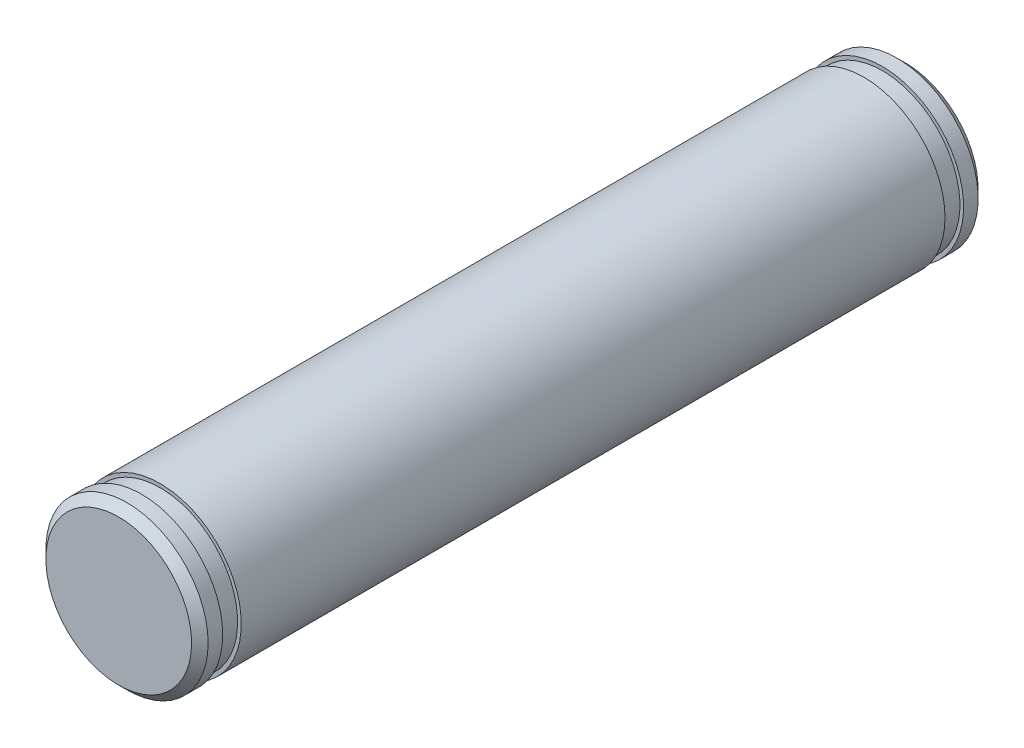
SolidWorks part; units mm, degrees
material "PET"
ref_plane "Front Plane" through (0, 0, 0) normal (0, 0, 1) x (1, 0, 0)
ref_plane "Top Plane" through (0, 0, 0) normal (0, 1, 0) x (1, 0, 0)
ref_plane "Right Plane" through (0, 0, 0) normal (1, 0, 0) x (0, 0, -1)
ref_axis "X AXIS" through (-88.99, 0, 0) along (1, 0, 0)
ref_axis "Y AXIS" through (0, 55, 0) along (0, -1, 0)
ref_axis "Z AXIS" through (0, 0, -88.99) along (0, 0, 1)
sketch "Sketch1" plane through (0, 0, 0) normal (1, 0, 0) x (0, 0, -1)
  line L0 (0, 0) -> (-23.504, 0) construction
  line L1 (0, 0) -> (60.325, 0)
  line L2 (0, 0) -> (0, 6.223)
  line L3 (0, 6.223) -> (60.325, 6.223)
  line L4 (60.325, 0) -> (60.325, 6.223)
  line L5 (88.99, 0) -> (-88.99, 0) construction
  dimension "D1" = 60.325
  dimension "D2" = 12.446
revolve "Revolve1" add sketch "Sketch1" angle 360 about L0
sketch "Sketch2" plane through (0, 0, 0) normal (1, 0, 0) x (0, 0, -1)
  line L5 (60.325, 6.223) -> (0, 6.223) construction
  line L6 (0, 0) -> (-9.7136, 0) construction
  line L7 (60.325, -6.223) -> (60.325, 6.223) construction
  line L8 (1.7526, 5.9436) -> (3.175, 5.9436)
  line L9 (1.7526, 5.9436) -> (1.7526, 6.7564)
  line L10 (1.7526, 6.7564) -> (3.175, 6.7564)
  line L11 (3.175, 5.9436) -> (3.175, 6.7564)
  line L12 (1.7526, 5.9436) -> (3.175, 6.7564) construction
  line L13 (1.7526, 6.7564) -> (3.175, 5.9436) construction
  line L14 (57.15, 5.9436) -> (58.5724, 5.9436)
  line L15 (57.15, 5.9436) -> (57.15, 6.7564)
  line L16 (57.15, 6.7564) -> (58.5724, 6.7564)
  line L17 (58.5724, 5.9436) -> (58.5724, 6.7564)
  line L18 (57.15, 5.9436) -> (58.5724, 6.7564) construction
  line L19 (57.15, 6.7564) -> (58.5724, 5.9436) construction
  line L20 (0, 6.223) -> (0, -6.223) construction
  line L21 (60.325, 6.223) -> (0, 6.223) construction
  line L22 (60.325, -6.223) -> (60.325, 6.223) construction
  line L23 (0, 6.223) -> (0, -6.223) construction
  point P7 (2.4638, 6.35)
  point P12 (57.8612, 6.35)
  dimension "D1" = 11.8872
  dimension "D2" = 1.4224
  dimension "D3" = 1.4224
  dimension "D4" = 1.7526
  dimension "D5" = 1.7526
  dimension "D6" = 13.5128
revolve "Cut-Revolve1" cut sketch "Sketch2" angle 360 about L6
chamfer "Chamfer1" distance 0.635 angle 45 2 edges at (-6.223, 0, -60.325) (-6.223, 0, 0)
